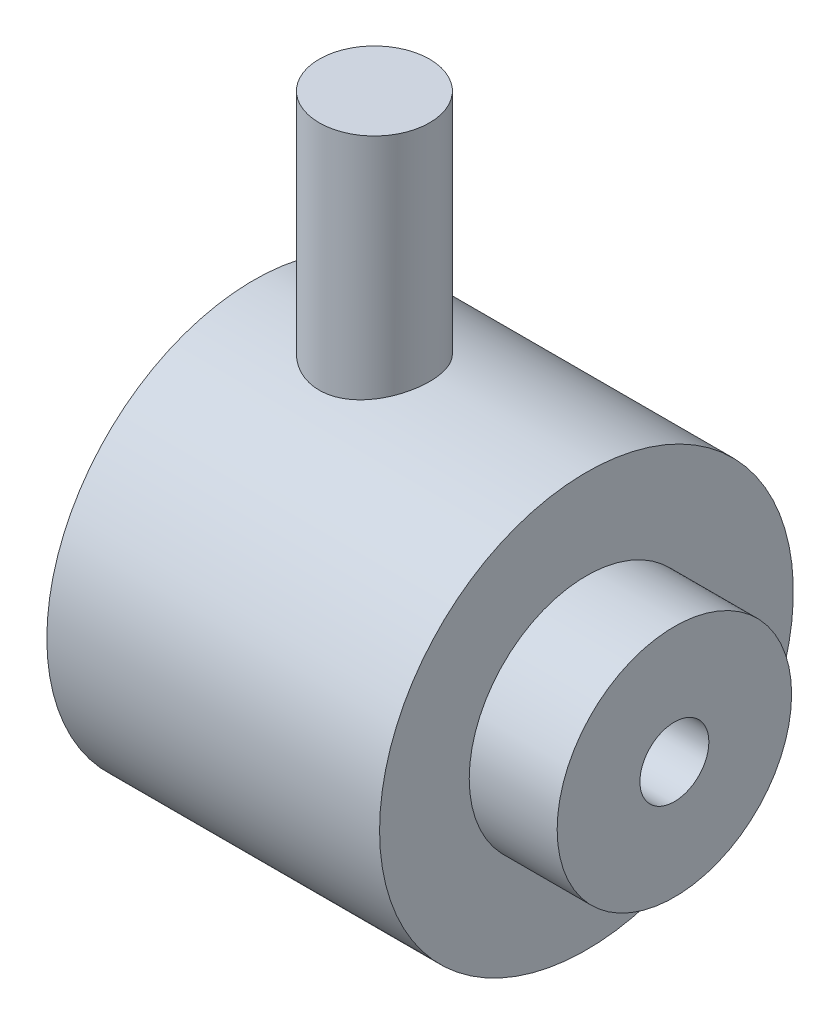
SolidWorks part; units mm, degrees
ref_plane "Plan de face" through (0, 0, 0) normal (0, 0, 1) x (1, 0, 0)
ref_plane "Plan de dessus" through (0, 0, 0) normal (0, 1, 0) x (1, 0, 0)
ref_plane "Plan de droite" through (0, 0, 0) normal (1, 0, 0) x (0, 0, -1)
sketch "Esquisse1" plane through (0, 0, 0) normal (0, 0, 1) x (1, 0, 0)
  line L0 (0, 0) -> (24.4, 0)
  line L1 (24.4, 0) -> (24.4, 6.8)
  line L2 (24.4, 6.8) -> (19.3, 6.8)
  line L3 (19.3, 6.8) -> (19.3, 12)
  line L4 (19.3, 12) -> (0, 12)
  line L5 (0, 12) -> (0, 0)
  dimension "D1" = 12
  dimension "D2" = 19.3
  dimension "D3" = 6.8
  dimension "D4" = 5.1
revolve "Révolution2" add sketch "Esquisse1" angle 360 about L0
sketch "Esquisse2" plane through (0, 0, 0) normal (0, 1, 0) x (1, 0, 0)
  line L0 (0, 12) -> (0, -12) construction
  circle A0 centre (7, 0) radius 3.2
  dimension "D1" = 6.4
  dimension "D2" = 7
extrude "Boss.-Extru.1" add sketch "Esquisse2" along normal blind 25
sketch "Esquisse3" plane through (24.4, 0, 0) normal (1, 0, 0) x (0, 0, -1)
  circle A0 centre (0, 0) radius 2
  dimension "D1" = 4
extrude "Enlèv. mat.-Extru.1" cut sketch "Esquisse3" against normal blind 14
